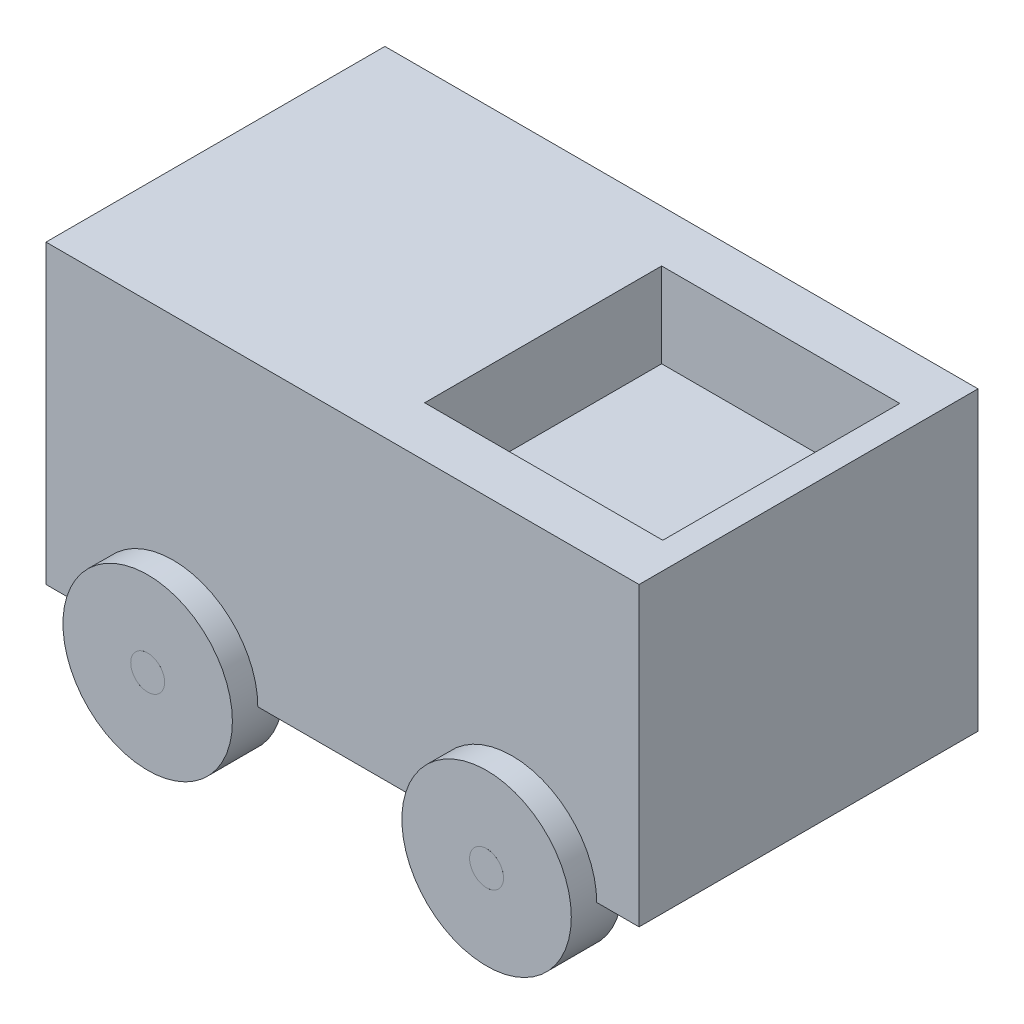
SolidWorks part; units mm, degrees
ref_plane "Front Plane" through (0, 0, 0) normal (0, 0, 1) x (1, 0, 0)
ref_plane "Top Plane" through (0, 0, 0) normal (0, 1, 0) x (1, 0, 0)
ref_plane "Right Plane" through (0, 0, 0) normal (1, 0, 0) x (0, 0, -1)
sketch "Sketch2" plane through (0, 0, 0) normal (0, 0, 1) x (1, 0, 0)
  line L1 (0, 0) -> (-70, 0)
  line L2 (0, 0) -> (0, -35)
  line L3 (0, -35) -> (-70, -35)
  line L4 (-70, 0) -> (-70, -35)
extrude "Boss-Extrude2" add sketch "Sketch2" along normal blind 40
sketch "Sketch3" plane through (0, 0, 0) normal (0, 1, 0) x (1, 0, 0)
  line L1 (-31.2286, -34.0804) -> (-3.1227, -34.0804)
  line L2 (-31.2286, -34.0804) -> (-31.2286, -6.1085)
  line L3 (-31.2286, -6.1085) -> (-3.1227, -6.1085)
  line L4 (-3.1227, -34.0804) -> (-3.1227, -6.1085)
extrude "Cut-Extrude1" cut sketch "Sketch3" against normal blind 10
sketch "Sketch4" plane through (0, 0, 40) normal (0, 0, 1) x (1, 0, 0)
  circle A2 centre (-15, -35) radius 10
  circle A4 centre (-55, -35) radius 10
extrude "Cut-Extrude2" cut sketch "Sketch4" against normal blind 3
sketch "Sketch5" plane through (0, 0, 0) normal (0, 0, -1) x (-1, 0, 0)
  circle A1 centre (15, -35) radius 10
  circle A3 centre (55, -35) radius 10
extrude "Cut-Extrude3" cut sketch "Sketch5" against normal blind 3
sketch "Sketch6" plane through (0, 0, 40) normal (0, 0, 1) x (1, 0, 0)
  circle A0 centre (-55, -35) radius 10
extrude "Boss-Extrude3" add sketch "Sketch6" along normal blind 3 and the other way blind 3
sketch "Sketch7" plane through (0, 0, 3) normal (0, 0, -1) x (-1, 0, 0)
  line L2 (45, -35) -> (65, -35) construction
  circle A2 centre (55, -35) radius 10
extrude "Boss-Extrude5" add sketch "Sketch7" along normal blind 6
sketch "Sketch8" plane through (0, 0, -3) normal (0, 0, -1) x (-1, 0, 0)
  circle A1 centre (55, -35) radius 2
extrude "Cut-Extrude5" cut sketch "Sketch8" against normal blind 46
sketch "Sketch9" plane through (0, 0, -3) normal (0, 0, -1) x (-1, 0, 0)
  circle A0 centre (55, -35) radius 2
extrude "Boss-Extrude8" add sketch "Sketch9" along normal blind 0.0001 and the other way blind 46.0001 contours A0
sketch "Sketch10" plane through (0, 0, 40) normal (0, 0, 1) x (1, 0, 0)
  circle A0 centre (-15, -35) radius 10
extrude "Boss-Extrude9" add sketch "Sketch10" along normal blind 3 and the other way blind 3
sketch "Sketch11" plane through (0, 0, 0) normal (0, 0, -1) x (-1, 0, 0)
  circle A0 centre (15, -35) radius 10
extrude "Boss-Extrude10" add sketch "Sketch11" along normal blind 3 and the other way blind 3
sketch "Sketch12" plane through (0, 0, -3) normal (0, 0, -1) x (-1, 0, 0)
  circle A1 centre (15, -35) radius 2
extrude "Cut-Extrude6" cut sketch "Sketch12" against normal blind 46
sketch "Sketch13" plane through (0, 0, -3) normal (0, 0, -1) x (-1, 0, 0)
  circle A0 centre (15, -35) radius 2
extrude "Boss-Extrude11" add sketch "Sketch13" along normal blind 0.001 and the other way blind 46.001
